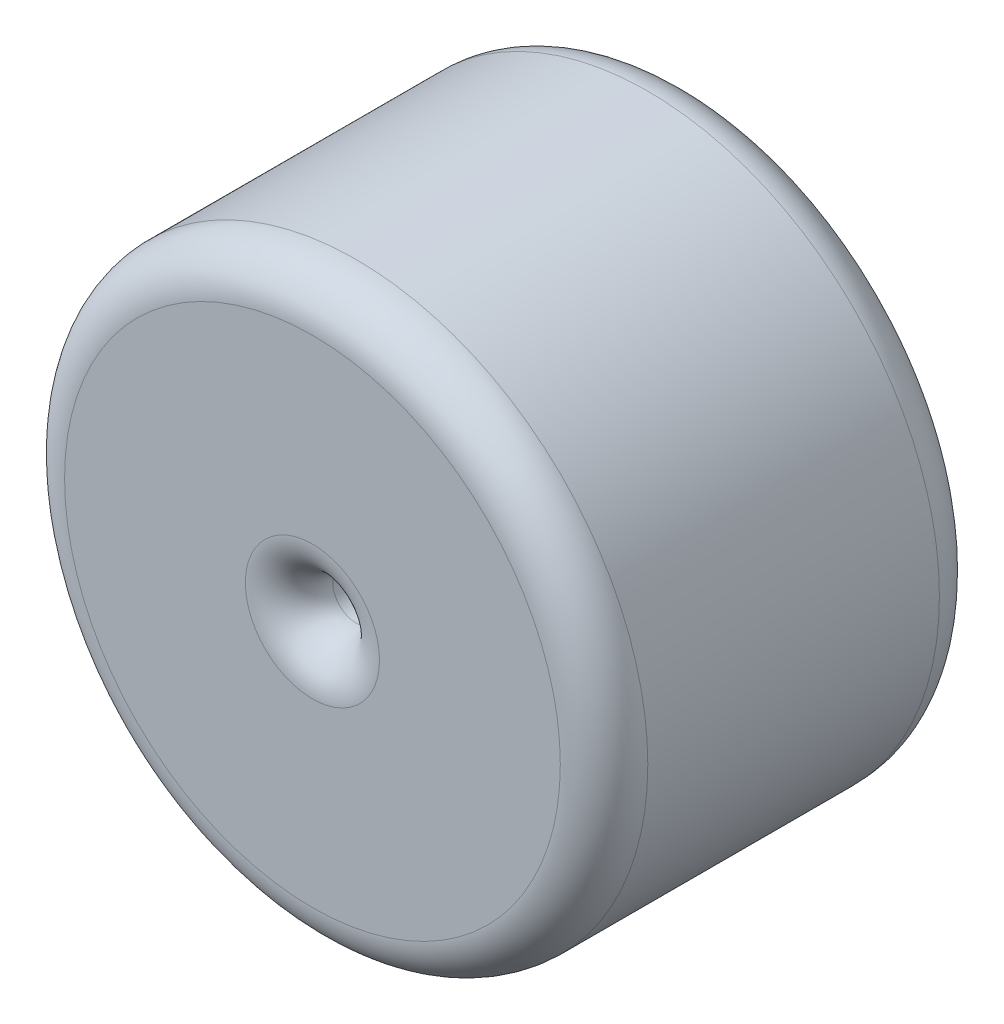
SolidWorks part; units mm, degrees
ref_plane "前视基准面" through (0, 0, 0) normal (0, 0, 1) x (1, 0, 0)
ref_plane "上视基准面" through (0, 0, 0) normal (0, 1, 0) x (1, 0, 0)
ref_plane "右视基准面" through (0, 0, 0) normal (1, 0, 0) x (0, 0, -1)
other "Configuration Table"
sketch "草图1" plane through (0, 0, 0) normal (0, 0, 1) x (1, 0, 0)
  circle A0 centre (0, 0) radius 20
  circle A1 centre (0, 0) radius 1.6
extrude "凸台-拉伸1" add sketch "草图1" along normal mid plane 26
fillet "圆角1" radius 3 4 edges at (1.6, 0, -13) (1.6, 0, 13) (20, 0, -13) (20, 0, 13) tangent propagation no
